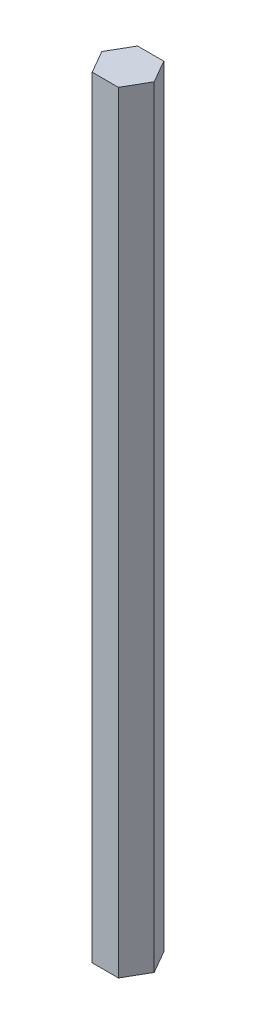
SolidWorks part; units mm, degrees
ref_plane "Front Plane" through (0, 0, 0) normal (0, 0, 1) x (1, 0, 0)
ref_plane "Top Plane" through (0, 0, 0) normal (0, 1, 0) x (1, 0, 0)
ref_plane "Right Plane" through (0, 0, 0) normal (1, 0, 0) x (0, 0, -1)
sketch "Sketch1" plane through (0, 0, 0) normal (0, 1, 0) x (1, 0, 0)
  line L9 (7.3323, 0) -> (3.6662, 6.35)
  line L10 (3.6662, 6.35) -> (-3.6662, 6.35)
  line L11 (-3.6662, 6.35) -> (-7.3323, 0)
  line L12 (-7.3323, 0) -> (-3.6662, -6.35)
  line L13 (-3.6662, -6.35) -> (3.6662, -6.35)
  line L14 (3.6662, -6.35) -> (7.3323, 0)
  circle A0 centre (0, 0) radius 6.35 construction
  dimension "D1" = 12.7
extrude "Boss-Extrude1" add sketch "Sketch1" along normal blind 215.9
